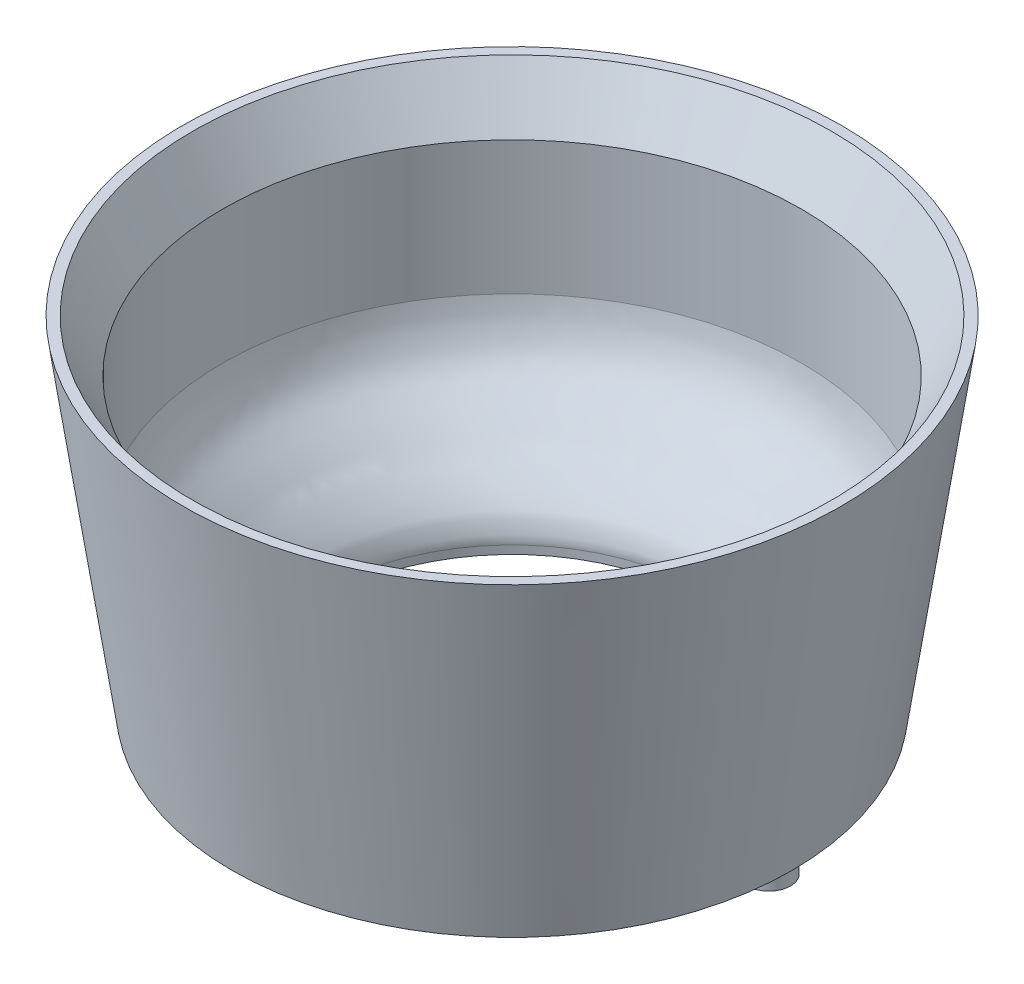
SolidWorks part; units mm, degrees
material "ABS PC"
ref_plane "Front Plane" through (0, 0, 0) normal (0, 0, 1) x (1, 0, 0)
ref_plane "Top Plane" through (0, 0, 0) normal (0, 1, 0) x (1, 0, 0)
ref_plane "Right Plane" through (0, 0, 0) normal (1, 0, 0) x (0, 0, -1)
sketch "Sketch1" plane through (0, 0, 0) normal (1, 0, 0) x (0, 0, -1)
  line L0 (26.0878, 274.978) -> (26.0878, 232.1195)
  line L2 (40.135, 299.274) -> (-40.135, 299.274) construction
  line L5 (0, 324) -> (3.2968, 324)
  line L8 (0, 324) -> (0, 0) construction
  line L9 (26.0878, 262.3641) -> (26.0878, 259.4973) construction
  line L12 (40.135, 302.9291) -> (40.135, 295.6188)
  line L16 (0, 0) -> (51.9362, 327.9125) construction
  line L17 (0, 324) -> (0, 332) construction
  line L18 (26.0878, 274.978) -> (26.0878, 268.978) construction
  line L19 (26.0878, 268.978) -> (26.0878, 248.978) construction
  line L20 (26.0878, 268.978) -> (42.6019, 268.978) construction
  line L21 (26.0878, 274.978) -> (43.5522, 274.978) construction
  line L22 (26.0878, 248.978) -> (39.4342, 248.978) construction
  line L23 (0, 0) -> (-51.9362, 327.9125) construction
  line L24 (-47.4003, 299.274) -> (-47.4003, 268.978) construction
  line L25 (-47.4003, 268.978) -> (-42.6019, 268.978) construction
  line L26 (0, 332) -> (0, 76.96) construction
  line L27 (0, 76.96) -> (400, 76.96) construction
  line L28 (0, 76.96) -> (-400, 76.96) construction
  line L29 (-200, 76.96) -> (-200, 183.96) construction
  line L30 (200, 76.96) -> (200, 183.96) construction
  line L31 (-200, 183.96) -> (-200, 182.57) construction
  line L32 (-200, 182.57) -> (400, 182.57) construction
  line L33 (-200, 182.57) -> (-400, 182.57) construction
  line L38 (0, 186.1152) -> (0, 324)
  line L39 (26.0878, 232.1195) -> (26.0878, 182.57) construction
  line L41 (21.6442, 226.0993) -> (26.0878, 226.0993)
  line L42 (26.0878, 226.0993) -> (26.0878, 186.1152)
  line L43 (26.0878, 186.1152) -> (0, 186.1152)
  line L44 (0, 0) -> (575.122, 0) construction
  arc A0 (-298.7691, 144.7791) -> (305.6579, 129.6043) centre (0, 0) cw construction
  spline S0 degree 3 poles (21.6442, 226.0993) (21.9584, 226.1509) (22.4049, 226.153) (22.896, 226.3321) (23.44, 226.7494) (24.2443, 227.2014) (25.0066, 227.9724) (25.5796, 228.9522) (25.8622, 230.393) (26.0228, 231.4436) (26.0878, 232.1195) knots 0 0 0 0 0.091924 0.112491 0.205673 0.333714 0.459267 0.602423 0.748839 1 1 1 1
  spline S1 degree 3 poles (3.2968, 324) (4.1972, 323.8396) (5.699, 323.816) (7.6935, 323.4297) (9.2722, 323.1563) (10.7507, 322.8538) (12.1816, 322.5577) (13.6372, 322.313) (14.8643, 321.9117) (15.9115, 321.5662) (16.81, 321.2491) (17.7339, 321.0149) (18.8379, 320.6416) (19.931, 320.1935) (21.0686, 319.6948) (22.141, 319.2627) (23.2156, 318.6856) (24.4371, 318.1163) (25.6762, 317.3518) (27.1066, 316.7518) (28.4318, 315.7832) (29.7322, 314.8939) (31.058, 313.93) (32.1959, 312.8581) (33.3378, 311.8503) (34.4539, 310.9646) (35.3895, 309.8867) (36.5078, 309.0949) (37.2942, 308.0208) (38.1233, 307.1238) (38.9048, 306.0961) (39.4724, 304.6349) (40.2774, 303.734) (40.135, 302.9291) knots 0 0 0 0 0.061585 0.100795 0.136831 0.1697 0.202569 0.235438 0.269088 0.289473 0.309858 0.333319 0.353706 0.388423 0.412965 0.437514 0.46634 0.495168 0.528354 0.564387 0.59925 0.638593 0.670824 0.709635 0.743897 0.773612 0.805519 0.839783 0.864953 0.89467 0.922395 0.951224 1 1 1 1
  spline S2 degree 3 poles (40.135, 295.6188) (39.9636, 294.7131) (39.7869, 293.3689) (39.1095, 291.6901) (38.6019, 290.4599) (37.8418, 289.2392) (36.9195, 288.2279) (35.9232, 287.2651) (34.974, 286.2515) (33.8311, 285.3463) (32.8233, 284.2966) (31.8701, 283.2868) (30.7668, 282.4387) (29.8742, 281.4644) (28.8604, 280.5152) (28.0567, 279.5119) (27.1438, 278.5569) (26.4968, 277.0287) (26.0081, 275.8567) (26.0878, 274.978) knots 0 0 0 0 0.108356 0.15601 0.210945 0.263562 0.322855 0.370186 0.4254 0.484692 0.539909 0.595126 0.646549 0.701764 0.749093 0.808384 0.85195 0.901837 1 1 1 1
  point P10 (0, 299.274)
  point P63 (0, 299.274)
  dimension "D3" = 9
  dimension "D1" = 40.135
  dimension "D2" = 324
  dimension "D4" = 8
  dimension "D5" = 3.2968
  dimension "D6" = 4.4435
  dimension "D7" = 6.0202
  dimension "D8" = 7.7403
  dimension "D9" = 6
  dimension "D10" = 20
  dimension "D11" = 9.317
  dimension "D12" = 10.7504
  dimension "D13" = 255.04
  dimension "D14" = 107
  dimension "D15" = 107
  dimension "D16" = 332
  dimension "D17" = 105.61
  dimension "D18" = 105.61
  dimension "D19" = 12.1838
  dimension "D20" = 13.6172
  dimension "D21" = 15.0506
  dimension "D22" = 15.9106
  dimension "D23" = 16.7707
  dimension "D24" = 17.7739
  dimension "D25" = 18.6341
  dimension "D26" = 20.0676
  dimension "D27" = 21.0708
  dimension "D28" = 22.0743
  dimension "D29" = 23.2209
  dimension "D30" = 24.3677
  dimension "D31" = 25.6578
  dimension "D32" = 27.0911
  dimension "D33" = 28.3811
  dimension "D34" = 29.8146
  dimension "D35" = 30.9613
  dimension "D36" = 32.2513
  dimension "D37" = 33.3981
  dimension "D38" = 34.4014
  dimension "D39" = 35.4048
  dimension "D40" = 36.5516
  dimension "D41" = 37.2681
  dimension "D42" = 38.1282
  dimension "D43" = 38.8449
  dimension "D44" = 39.4183
  dimension "D45" = 39.9917
  dimension "D46" = 323.8567
  dimension "D47" = 323.7133
  dimension "D48" = 323.4267
  dimension "D49" = 323.1399
  dimension "D50" = 322.8533
  dimension "D51" = 322.5666
  dimension "D52" = 322.2799
  dimension "D53" = 321.8499
  dimension "D54" = 321.5632
  dimension "D55" = 321.2765
  dimension "D56" = 320.9899
  dimension "D57" = 320.7031
  dimension "D58" = 320.1297
  dimension "D59" = 319.6998
  dimension "D60" = 319.2698
  dimension "D61" = 318.6965
  dimension "D62" = 318.1231
  dimension "D63" = 317.4064
  dimension "D64" = 316.6897
  dimension "D65" = 315.8296
  dimension "D66" = 314.8263
  dimension "D67" = 313.9663
  dimension "D68" = 312.8195
  dimension "D69" = 311.8162
  dimension "D70" = 310.9562
  dimension "D71" = 309.9528
  dimension "D72" = 308.9493
  dimension "D73" = 308.0893
  dimension "D74" = 307.086
  dimension "D75" = 306.0826
  dimension "D76" = 304.9359
  dimension "D77" = 303.9325
  dimension "D78" = 302.9291
sketch "Sketch2" plane through (0, 0, 0) normal (1, 0, 0) x (0, 0, -1)
  line L0 (0, 324) -> (3.2968, 324) construction
  line L1 (26.5078, 274.997) -> (26.5078, 273.8486)
  line L2 (40.5477, 295.5407) -> (40.5477, 314.2386)
  line L3 (40.135, 295.6188) -> (40.135, 302.9302) construction
  line L4 (40.135, 295.6188) -> (26.0878, 274.978) construction
  line L5 (0, 324.42) -> (3.4084, 324.42) construction
  line L6 (3.2968, 324) -> (40.135, 302.9302) construction
  line L7 (3.4084, 324.42) -> (40.555, 303.1738) construction
  line L8 (26.0878, 274.978) -> (26.0878, 232.1195) construction
  line L9 (40.555, 295.4895) -> (26.435, 274.7417) construction
  line L10 (0, 5) -> (0, 407.9498) construction
  line L12 (26.5078, 273.8486) -> (38.5078, 273.8486) construction
  line L13 (26.5078, 274.997) -> (26.5078, 232.1195) construction
  line L14 (38.5078, 273.8486) -> (45.76, 323.5611) construction
  line L17 (40.5477, 314.2386) -> (45.93, 323.5611) construction
  line L18 (45.93, 323.5611) -> (45.76, 323.5611) construction
  line L19 (0, 186.1152) -> (0, 324) construction
  line L20 (0, 324) -> (0, 332) construction
  line L21 (40.555, 295.4895) -> (40.555, 303.1738) construction
  line L22 (0, 5) -> (47.1644, 328.2999) construction
  line L23 (45.93, 323.5611) -> (46.473, 323.5611) construction
  line L24 (46.473, 323.5611) -> (39.2208, 273.8486) construction
  line L25 (39.2208, 273.8486) -> (26.5078, 273.8486)
  line L26 (44.7753, 321.5611) -> (46.1813, 321.5611)
  line L27 (44.7753, 321.5611) -> (40.5477, 314.2386)
  line L28 (46.1813, 321.5611) -> (39.2208, 273.8486)
  spline S0 degree 1 poles (40.5477, 295.5407) (26.5078, 274.997) knots 0 0 1 1 construction
  spline S1 degree 3 poles (40.135, 295.6188) (39.9636, 294.7131) (39.7869, 293.3689) (39.1095, 291.6901) (38.6019, 290.4599) (37.8418, 289.2392) (36.9195, 288.2279) (35.9232, 287.2651) (34.974, 286.2515) (33.8311, 285.3463) (32.8233, 284.2966) (31.8701, 283.2868) (30.7668, 282.4387) (29.8742, 281.4644) (28.8604, 280.5152) (28.0567, 279.5119) (27.1438, 278.5569) (26.4968, 277.0287) (26.0081, 275.8567) (26.0878, 274.978) knots 0 0 0 0 0.108356 0.15601 0.210945 0.263562 0.322855 0.370186 0.4254 0.484692 0.539909 0.595126 0.646549 0.701764 0.749093 0.808384 0.85195 0.901837 1 1 1 1 construction
  spline S2 degree 3 poles (40.5477, 295.5407) (40.4477, 295.0127) (40.2928, 293.9708) (39.9309, 292.5875) (39.5162, 291.5815) (39.1084, 290.578) (38.4397, 289.317) (37.3314, 288.0326) (36.3684, 287.1154) (35.6302, 286.3401) (35.0165, 285.7627) (34.3943, 285.2472) (33.6355, 284.5566) (32.9204, 283.7714) (32.1297, 282.9861) (31.4852, 282.4595) (30.915, 281.9635) (30.3717, 281.3913) (29.7828, 280.8046) (29.2276, 280.2622) (28.7248, 279.6749) (28.1804, 279.0397) (27.6518, 278.4702) (27.3081, 277.8768) (26.9952, 277.1272) (26.598, 276.1645) (26.4648, 275.4705) (26.5078, 274.997) knots 0 0 0 0 0.062544 0.125088 0.15636 0.187632 0.250176 0.31272 0.375264 0.406536 0.437808 0.46908 0.500352 0.562896 0.594168 0.62544 0.656713 0.687985 0.719257 0.750529 0.781801 0.813073 0.844345 0.875617 0.906889 0.938161 1.000705 1.000705 1.000705 1.000705
  point P38 (0, 328)
  dimension "D4" = 1.1484
  dimension "D5" = 8.3
  dimension "D6" = 30
  dimension "D7" = 45.93
  dimension "D8" = 40.39
  dimension "D9" = 8.3
  dimension "D10" = 40.5477
  dimension "D3" = 12
  dimension "D11" = 18.6979
  dimension "D12" = 2
  dimension "D13" = 5
  dimension "D1" = 0.42
  dimension "D2" = 0.42
revolve "Revolve6" add sketch "Sketch2" angle 360 about L10
sketch "Sketch3" plane through (0, 0, 0) normal (1, 0, 0) x (0, 0, -1)
  line L0 (44.1979, 321.5611) -> (40.5477, 314.2386) construction
  line L3 (46.1813, 321.5611) -> (-46.1813, 321.5611) construction
  line L4 (44.7753, 321.5611) -> (-44.7753, 321.5611) construction
  line L5 (40.5477, 314.2386) -> (-40.5477, 314.2386) construction
  line L6 (40.5477, 314.2386) -> (54.812, 333.8718)
  line L8 (54.812, 333.8718) -> (54.812, 347.837)
  line L9 (54.812, 347.837) -> (0, 347.837)
  line L10 (0, 347.837) -> (0, 311.6751)
  line L11 (0, 186.1152) -> (0, 324) construction
  line L12 (0, 311.6751) -> (40.5477, 311.6751)
  line L13 (40.5477, 311.6751) -> (40.5477, 314.2386)
  dimension "D1" = 36
  dimension "D2" = 54.812
revolve "Cut-Revolve1" [suppressed] cut sketch "Sketch3" angle 360 about L10
sketch "Sketch4" plane through (0, 273.8486, 0) normal (0, -1, 0) x (1, 0, 0)
  line L0 (0, 0) -> (36, 0) construction
  line L1 (0, 0) -> (-31.1769, 18) construction
  circle A0 centre (0, 0) radius 36 construction
  circle A1 centre (-31.1769, 18) radius 3
  circle A2 centre (36, 0) radius 3
  dimension "D1" = 72
  dimension "D3" = 6
  dimension "D4" = 6
  dimension "D2" = 150
extrude "Boss-Extrude1" add sketch "Sketch4" along normal blind 2
sketch "Sketch5" [suppressed] plane through (0, 263.8486, 0) normal (0, -1, 0) x (1, 0, 0)
  circle A0 centre (36, 0) radius 3.175
  circle A1 centre (-31.1769, 18) radius 3.175
  dimension "D1" = 6.35
  dimension "D2" = 6.35
extrude "Boss-Extrude2" [suppressed] add sketch "Sketch5" along normal blind 5
chamfer "Chamfer2" [suppressed] distance 9 angle 4
sketch "Sketch7" plane through (0, 0, 0) normal (1, 0, 0) x (0, 0, -1)
  line L0 (0, 5) -> (0, 407.9498) construction
  line L1 (26.5078, 273.8486) -> (39.2208, 273.8486) construction
  line L2 (39.2208, 273.8486) -> (39.2208, 272.3194)
  line L4 (26.5078, 273.8486) -> (26.5078, 274.3486)
  line L5 (26.5078, 274.3486) -> (39.2208, 274.3486)
  line L6 (39.2208, 274.3486) -> (39.2208, 273.8486)
  circle A0 centre (0, -0.122) radius 275.25 construction
  arc A1 (39.2208, 272.3194) -> (26.5078, 273.8486) centre (0, -0.122) ccw
  dimension "D1" = 550.5
  dimension "D2" = 0.5
revolve "Revolve7" [suppressed] add sketch "Sketch7" angle 360 about L10
sketch "Sketch9" plane through (0, 271.8486, 0) normal (0, -1, 0) x (1, 0, 0)
  circle A0 centre (36, 0) radius 1.5
  circle A1 centre (-31.1769, 18) radius 1.5
  dimension "D1" = 3
  dimension "D2" = 3
extrude "Cut-Extrude1" cut sketch "Sketch9" against normal blind 6
sketch "Sketch10" plane through (0, 271.8486, 0) normal (0, -1, 0) x (1, 0, 0)
  circle A0 centre (36, 0) radius 2
  circle A1 centre (-31.1769, 18) radius 2
  dimension "D1" = 4
  dimension "D2" = 4
extrude "Cut-Extrude2" cut sketch "Sketch10" against normal blind 0.5
chamfer "Chamfer3" distance 0.55 angle 45 2 edges at (36, 271.8486, -2) (-31.1769, 271.8486, 16)
